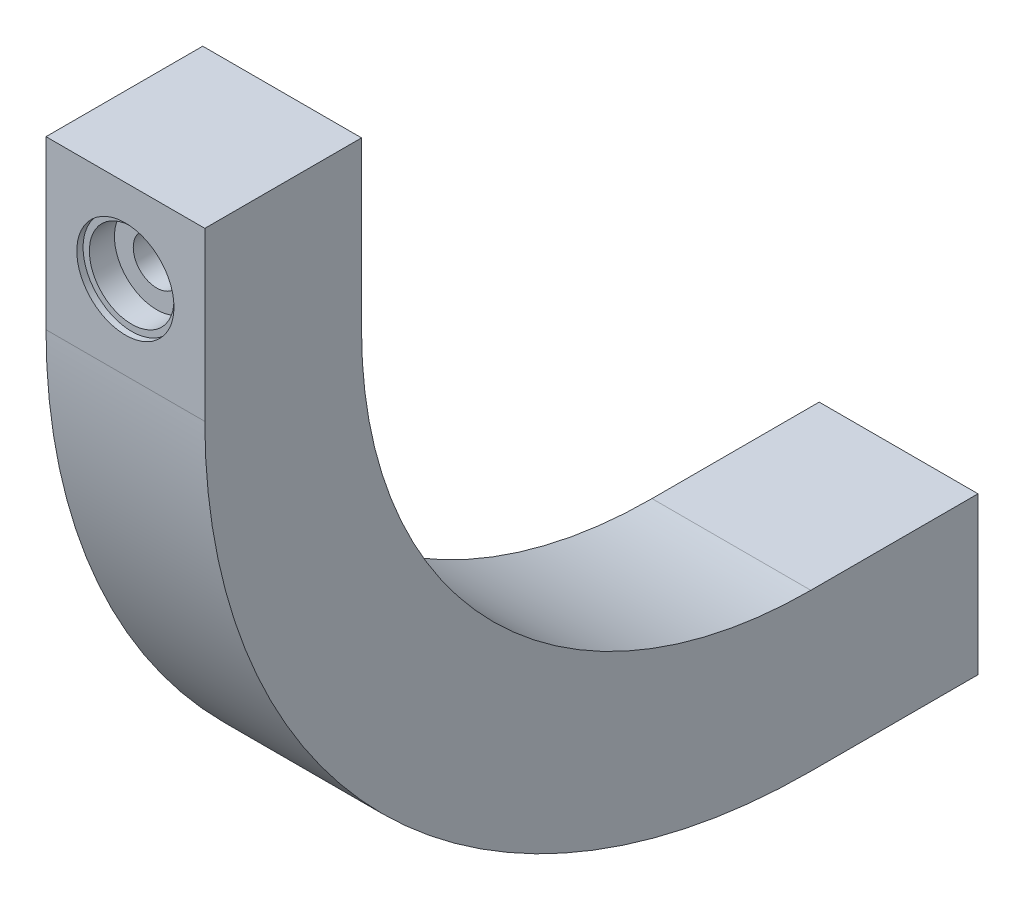
SolidWorks part; units mm, degrees
ref_plane "Front Plane" through (0, 0, 0) normal (0, 0, 1) x (1, 0, 0)
ref_plane "Top Plane" through (0, 0, 0) normal (0, 1, 0) x (1, 0, 0)
ref_plane "Right Plane" through (0, 0, 0) normal (1, 0, 0) x (0, 0, -1)
ref_axis "Z" through (0, 0, 109.5585) along (0, 0, -1)
ref_axis "X" through (8.36, 0, 0) along (-1, 0, 0)
sketch "Sketch4" plane through (0, 0, 0) normal (0, 0, 1) x (1, 0, 0)
  circle A0 centre (0, 0) radius 50 construction
  dimension "D1" = 100
sketch "Sketch5" plane through (0, 0, 0) normal (1, 0, 0) x (0, 0, -1)
  line L0 (-51, 8) -> (-51, 0)
  line L1 (-51, 0) -> (-51, -8)
  line L2 (-66, -8) -> (-66, 8)
  line L6 (-66, 8) -> (-51, 8)
  line L12 (-109.5585, 0) -> (-13.0351, 0) construction
  line L13 (0, 0) -> (-14.9091, -14.9091) construction
  line L14 (0, 0) -> (7.0065, 0) construction
  line L15 (0, -51) -> (-8, -51)
  line L16 (8, -51) -> (0, -51)
  line L17 (-8, -66) -> (8, -66)
  line L18 (8, -66) -> (8, -51)
  circle A0 centre (0, 0) radius 14 construction
  arc A1 (-51, -8) -> (-8, -51) centre (-8, -8) ccw
  arc A2 (-66, -8) -> (-8, -66) centre (-8, -8) ccw
  point P2 (9.4307, -21)
  point P4 (0, -2.1363)
  dimension "D1" = 28
  dimension "D4" = 8
  dimension "D2" = 45
  dimension "D3" = 15
  dimension "D5" = 51
sketch "Sketch6" plane through (0, 0, 0) normal (0, 1, 0) x (1, 0, 0)
  circle A0 centre (0, 0) radius 50 construction
  dimension "D1" = 100
extrude "Boss-Extrude1" add sketch "Sketch5" along normal blind 7.6 and the other way blind 7.6
sketch "Sketch7" plane through (0, 0, 0) normal (0, 0, 1) x (1, 0, 0)
  circle A0 centre (0, 0) radius 2.25
  dimension "D1" = 4.5
extrude "Cut-Extrude1" cut sketch "Sketch7" along normal through all
ref_axis "Y" through (0, -9.3489, 0) along (0, -1, 0)
sketch "Sketch16" plane through (0, 0, 0) normal (1, 0, 0) x (0, 0, -1)
  line L0 (0, -67) -> (0, 0) construction
  dimension "D1" = 67
ref_plane "Plane1" through (0, -67, 0) normal (0, 1, 0) x (1, 0, 0)
ref_axis "CX" through (0, -67, 4.4) along (0, 0, -1)
ref_plane "Plane2" through (0, 0, 0) normal (0, 0, -1) x (0, 1, 0)
ref_plane "Plane3" through (0, 0, 0) normal (1, 0, 0) x (0, 0, -1)
ref_axis "CZ" through (0, -8.7018, 0) along (0, -1, 0)
ref_axis "CY" through (-0.6471, -67, 0) along (1, 0, 0)
ref_point "CO"
sketch "Sketch15" plane through (0, -66, 0) normal (0, -1, 0) x (1, 0, 0)
  circle A0 centre (0, 0) radius 2.05
  dimension "D1" = 4.1
extrude "Cut-Extrude11" cut sketch "Sketch15" against normal blind 10
sketch "Sketch18" plane through (0, 0, 0) normal (1, 0, 0) x (0, 0, -1)
  line L0 (-66, 4.65) -> (-66, 0)
  line L1 (-66, 0) -> (-63, 0)
  line L2 (-63, 0) -> (-63, 4.05)
  line L3 (-63, 4.05) -> (-65.4, 4.05)
  line L4 (-65.4, 4.05) -> (-65.4, 4.65)
  line L5 (-65.4, 4.65) -> (-66, 4.65)
  line L6 (-68.6876, 0) -> (-58.5, 0) construction
  line L7 (-58.5, 0) -> (-58.5, 8) construction
  line L8 (-51.6, 4.65) -> (-51, 4.65)
  line L9 (-51.6, 4.05) -> (-51.6, 4.65)
  line L10 (-54, 4.05) -> (-51.6, 4.05)
  line L11 (-54, 0) -> (-54, 4.05)
  line L12 (-51, 0) -> (-54, 0)
  line L13 (-51, 4.65) -> (-51, 0)
  line L14 (-109.5585, 0) -> (-13.0351, 0) construction
  line L15 (-66, 8) -> (-51, 8) construction
  line L16 (-66, -8) -> (-66, 8) construction
  dimension "D1" = 0.6
  dimension "D2" = 8.1
  dimension "D3" = 3
  dimension "D4" = 4.65
revolve "Cut-Revolve1" cut sketch "Sketch18" angle 360 about axis through (0, 0, 109.5585) along (0, 0, -1)
equation "\"rbracket-width\"= \"L2Thickness\" + 0.2"
equation "\"EyeCaptureRadius\"= ( \"EyeDiameter\" + \"EyeClearance\" ) / 2"
equation "\"rbracket_planetocenterline_dist\"= \"BasePlaneDistance\""
equation "\"EyeDiameter\" = 100"
equation "\"BasePlaneDistance\" = \"EyeDiameter\"/2+\"L2Thickness\"+\"EyeClearance\""
equation "\"EyeClearance\" = 2"
equation "\"D1@Sketch4\"=\"EyeDiameter\""
equation "\"D1@Sketch6\"=\"EyeDiameter\""
equation "\"D1@Boss-Extrude1\"=\"rbracket-width\"/2"
equation "\"D2@Boss-Extrude1\"=\"rbracket-width\"/2"
equation "\"L2Thickness\" = 15"
equation "\"D3@Sketch5\"=\"L2Thickness\""
equation "\"D5@Sketch5\"=(\"EyeDiameter\"+\"EyeClearance\")/2"
equation "\"BearingThickness\"= 6"
equation "\"BearingOD\"=4.5"
equation "\"OuterBearingProudDistance\"= 0"
equation "\"FlangeOD\"=7.5"
equation "\"FlangeThickness\"= 0.75"
equation "\"PrinterFilamentThickness\"= 0.1'For setting distances for things like pressfits"
equation "\"ApplyPrinterOffset\"= 1'Set to 0 for line-to-line. Set to 1 for applying guestimate dimensions to make the printer produce good parts"
equation "\"D1@Cut-Extrude11\"=\"shaft_diameter\"*2.5"
equation "\"D1@Sketch16\"=\"BasePlaneDistance\""
equation "\"D2@Sketch18\"=\"ApplyPrinterOffset\"*\"PrinterFilamentThickness\" + 8"
equation "\"D4@Sketch18\"=4.6 + \"ApplyPrinterOffset\"*\"PrinterFilamentThickness\"/2"
equation "\"L2_ID\" = 20"
equation "\"vx\" = 0"
equation "\"vy\" = 0"
equation "\"vz\" = 100"
equation "\"parametric_end\" = 1"
equation "\"Rw_3_xx\" = -(\"vz\")/sqr((\"vx\")^2 + (\"vz\")^2)"
equation "\"Rw_3_xy\" = 0"
equation "\"Rw_3_xz\" = (\"vx\")/sqr((\"vx\")^2 + (\"vz\")^2)"
equation "\"Rw_3_zx\" = (\"vx\")/sqr((\"vx\")^2 + (\"vy\")^2 + (\"vz\")^2)"
equation "\"Rw_3_zy\" = (\"vy\")/sqr((\"vx\")^2 + (\"vy\")^2 + (\"vz\")^2)"
equation "\"Rw_3_zz\" = (\"vz\")/sqr((\"vx\")^2 + (\"vy\")^2 + (\"vz\")^2)"
equation "\"Rw_3_yx\" = (\"vx\")*(\"vy\")/sqr((\"vx\")^4 + (\"vx\")^2*(\"vy\")^2 + 2*(\"vx\")^2*(\"vz\")^2 + (\"vy\")^2*(\"vz\")^2 + (\"vz\")^4)"
equation "\"Rw_3_yy\" = -sqr((\"vx\")^2 + (\"vz\")^2)/sqr((\"vx\")^2 + (\"vy\")^2 + (\"vz\")^2)"
equation "\"Rw_3_yz\" = (\"vy\")*(\"vz\")/sqr((\"vx\")^4 + (\"vx\")^2*(\"vy\")^2 + 2*(\"vx\")^2*(\"vz\")^2 + (\"vy\")^2*(\"vz\")^2 + (\"vz\")^4)"
equation "\"O2Targx\" = -\"BasePlaneDistance\"*(\"vx\")*(\"vy\")/sqr((\"vx\")^4 + (\"vx\")^2*(\"vy\")^2 + 2*(\"vx\")^2*(\"vz\")^2 + (\"vy\")^2*(\"vz\")^2 + (\"vz\")^4)"
equation "\"O2Targy\" = \"BasePlaneDistance\"*sqr((\"vx\")^2 + (\"vz\")^2)/sqr((\"vx\")^2 + (\"vy\")^2 + (\"vz\")^2)"
equation "\"O2Targz\" = -\"BasePlaneDistance\"*(\"vy\")*(\"vz\")/sqr((\"vx\")^4 + (\"vx\")^2*(\"vy\")^2 + 2*(\"vx\")^2*(\"vz\")^2 + (\"vy\")^2*(\"vz\")^2 + (\"vz\")^4)"
equation "\"O2Targx_0\" = -(\"BasePlaneDistance\")*sqr((\"vx\")^2 + (\"vz\")^2)/sqr((\"vx\")^2 + (\"vy\")^2 + (\"vz\")^2)"
equation "\"O2Targy_0\" = -(\"BasePlaneDistance\")*(\"vy\")*(\"vz\")/sqr((\"vx\")^4 + (\"vx\")^2*(\"vy\")^2 + 2*(\"vx\")^2*(\"vz\")^2 + (\"vy\")^2*(\"vz\")^2 + (\"vz\")^4)"
equation "\"O2Targz_0\" = (\"BasePlaneDistance\")*(\"vx\")*(\"vy\")/sqr((\"vx\")^4 + (\"vx\")^2*(\"vy\")^2 + 2*(\"vx\")^2*(\"vz\")^2 + (\"vy\")^2*(\"vz\")^2 + (\"vz\")^4) + (\"BasePlaneDistance\")"
equation "\"theta2_s1\" = arcsin(((\"BasePlaneDistance\") - (\"O2Targz_0\"))/(\"BasePlaneDistance\")) + pi"
equation "\"theta2_s2\" = -arcsin(((\"BasePlaneDistance\") - (\"O2Targz_0\"))/(\"BasePlaneDistance\"))"
equation "\"theta1_s1\" = arcsin((\"O2Targy_0\")/((\"BasePlaneDistance\")*cos((\"Theta2\")))) + pi"
equation "\"theta1_s2\" = -arcsin((\"O2Targy_0\")/((\"BasePlaneDistance\")*cos((\"Theta2\"))))"
equation "\"theta1_s3\" = -arccos(-(\"O2Targx_0\")/((\"BasePlaneDistance\")*cos((\"Theta2\")))) + 2*pi"
equation "\"theta1_s4\" = arccos(-(\"O2Targx_0\")/((\"BasePlaneDistance\")*cos((\"Theta2\"))))"
equation "\"Theta1\" = \"theta1_s2\" 'so far, theta1_s1 and theta1_s4 have agreed, and they agree with the sw constraint solver"
equation "\"Theta2\" = \"theta2_s2\""
equation "\"o2_x\" = -(\"BasePlaneDistance\")*cos((\"Theta1\"))*cos((\"Theta2\"))"
equation "\"o2_y\" = -(\"BasePlaneDistance\")*sin((\"Theta1\"))*cos((\"Theta2\"))"
equation "\"o2_z\" = (\"BasePlaneDistance\")*(sin((\"Theta2\")) + 1)"
equation "\"o1_x\" = (\"BasePlaneDistance\")*sin((\"Theta1\"))"
equation "\"o1_y\" = -(\"BasePlaneDistance\")*cos((\"Theta1\"))"
equation "\"o1_z\" = (\"BasePlaneDistance\")"
equation "\"Actuator1_Theta\" = atn(\"vx\"/\"vz\") 'ik solution for the single link joint"
equation "\"Actuator2_Theta\" = \"Theta1\"  'ik solution for the double link joint"
equation "\"MotorBaseThickness\" = 3 "
equation "\"BaseThickness\" = 3 "
equation "\"EncoderToMagnetAirgap\" = 1 'Encoder to magnet airgap"
equation "\"EncoderHeight\" = 1.192  'Height of the encoder"
equation "\"MagnetThickness\" = 0.5  'Magnet thickness"
equation "\"pcb_thickness\" = 1.6  'Thickness of the PCB"
equation "\"pcb_outer_diameter\" = 32 'the OD of the pcb"
equation "\"shaft_diameter\" = 4"
equation "\"D1@Sketch15\"=\"shaft_diameter\"+\"ApplyPrinterOffset\"*\"PrinterFilamentThickness\""
